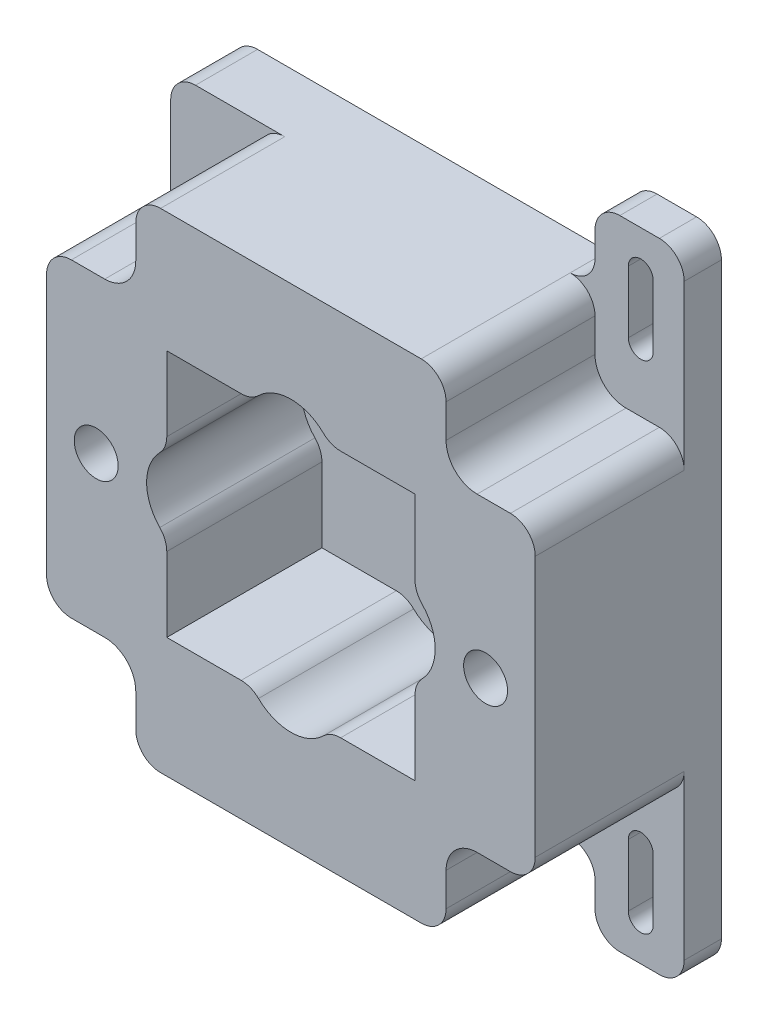
SolidWorks part; units mm, degrees
ref_plane "Front Plane" through (0, 0, 0) normal (0, 0, 1) x (1, 0, 0)
ref_plane "Top Plane" through (0, 0, 0) normal (0, 1, 0) x (1, 0, 0)
ref_plane "Right Plane" through (0, 0, 0) normal (1, 0, 0) x (0, 0, -1)
sketch "Sketch1" plane through (0, 0, 0) normal (0, 0, 1) x (1, 0, 0)
  line L1 (25, -25) -> (-25, -25)
  line L3 (25, -25) -> (25, 25)
  line L6 (25, 25) -> (-25, 25)
  line L7 (-25, -25) -> (-25, 25)
  line L8 (25, -25) -> (-25, 25) construction
  line L9 (25, 25) -> (-25, -25) construction
  point P0 (0, 0)
  dimension "D1" = 50
extrude "Boss-Extrude1" add sketch "Sketch1" along normal blind 6.35 contours L7 L1 L3 L6 region at (0, 0, 0)
sketch "Sketch6" plane through (0, 0, 6.35) normal (0, 0, 1) x (1, 0, 0)
  line L0 (15.875, 25) -> (-15.875, 25)
  line L1 (12.7, -12.7) -> (-12.7, -12.7)
  line L2 (12.7, -12.7) -> (12.7, 12.7)
  line L3 (12.7, 12.7) -> (-12.7, 12.7)
  line L4 (-12.7, -12.7) -> (-12.7, 12.7)
  line L5 (12.7, -12.7) -> (-12.7, 12.7) construction
  line L6 (12.7, 12.7) -> (-12.7, -12.7) construction
  line L7 (-25, -15.875) -> (-25, 15.875)
  line L8 (15.875, -25) -> (-15.875, -25)
  line L9 (25, -15.875) -> (25, 15.875)
  line L10 (-15.875, 19.05) -> (-15.875, 25)
  line L11 (-19.05, 15.875) -> (-25, 15.875)
  line L12 (25, 25) -> (-25, 25) construction
  line L13 (-25, -25) -> (-25, 25) construction
  line L14 (19.05, 15.875) -> (25, 15.875)
  line L15 (15.875, 19.05) -> (15.875, 25)
  line L16 (15.875, -19.05) -> (15.875, -25)
  line L17 (19.05, -15.875) -> (25, -15.875)
  line L18 (-19.05, -15.875) -> (-25, -15.875)
  line L19 (-15.875, -19.05) -> (-15.875, -25)
  line L20 (25, -25) -> (25, 25) construction
  line L21 (25, -25) -> (-25, -25) construction
  line L22 (0, 0) -> (0, -42.4127) construction
  line L23 (25, -25) -> (-25, -25) construction
  line L24 (-25, -25) -> (-25, 25) construction
  line L25 (0, 0) -> (48.4549, 0) construction
  arc A0 (-19.05, 15.875) -> (-15.875, 19.05) centre (-19.05, 19.05) ccw
  arc A1 (15.875, 19.05) -> (19.05, 15.875) centre (19.05, 19.05) ccw
  arc A2 (19.05, -15.875) -> (15.875, -19.05) centre (19.05, -19.05) ccw
  arc A3 (-15.875, -19.05) -> (-19.05, -15.875) centre (-19.05, -19.05) ccw
  point P0 (0, 0)
  point P33 (0, 0)
  dimension "D4" = 3.175
  dimension "D1" = 25.4
  dimension "D2" = 31.75
  dimension "D3" = 31.75
extrude "Boss-Extrude3" add sketch "Sketch6" along normal blind 12.7 contours L19 L8 L16 L17 L9 L14 L15 L0 L10 L11 L7 L18 L1 L4 L3 L2 region at (15.1679, 22.025, 6.35)
sketch "Sketch10" plane through (0, 0, 19.05) normal (0, 0, 1) x (1, 0, 0)
  line L12 (-12.7, -12.7) -> (12.7, -12.7)
  line L13 (12.7, -12.7) -> (12.7, 12.7)
  line L14 (12.7, 12.7) -> (-12.7, 12.7)
  line L15 (-12.7, 12.7) -> (-12.7, -12.7)
  dimension "D1" = 25.4
  dimension "D2" = 25.4
extrude "Cut-Extrude2" cut sketch "Sketch10" against normal blind 15.875
fillet "Fillet3" radius 2.54 8 edges at (-15.875, -25, 12.7) (15.875, -25, 12.7) (25, -15.875, 12.7) (25, 15.875, 12.7) (15.875, 25, 12.7) (-15.875, 25, 12.7) (-25, -15.875, 12.7) (-25, 15.875, 12.7)
sketch "Sketch11" plane through (0, 0, 6.35) normal (0, 0, 1) x (1, 0, 0)
  line L0 (33.4433, 630.1123) -> (32.9175, 610.2798) construction
  line L1 (25, -25) -> (15.875, -25)
  line L2 (25, -25) -> (25, -32.62)
  line L3 (25, -32.62) -> (15.875, -32.62)
  line L4 (15.875, -25) -> (15.875, -32.62)
  line L5 (15.875, -19.05) -> (15.875, -22.46) construction
  dimension "D1" = 7.62
extrude "Boss-Extrude4" add sketch "Sketch11" against normal up to surface (6.35 mm away) up to face at (0, 0, 0)
fillet "Fillet4" radius 2.54 2 edges at (15.875, -32.62, 3.175) (25, -32.62, 3.175)
sketch "Sketch12" plane through (0, 0, 6.35) normal (0, 0, 1) x (1, 0, 0)
  line L0 (25, -30.08) -> (25, -13.335) construction
  line L2 (19.05, -15.875) -> (22.46, -15.875) construction
  line L3 (20.555, -28.575) -> (20.555, -22.225) construction
  line L4 (19.285, -28.575) -> (19.285, -22.225)
  line L5 (21.825, -28.575) -> (21.825, -22.225)
  circle A0 centre (20.555, -25.4) radius 1.27
  arc A1 (19.285, -28.575) -> (21.825, -28.575) centre (20.555, -28.575) ccw
  arc A2 (21.825, -22.225) -> (19.285, -22.225) centre (20.555, -22.225) ccw
  point P9 (20.555, -25.4)
  dimension "D1" = 2.54
  dimension "D2" = 9.525
  dimension "D3" = 6.35
  dimension "D4" = 4.445
extrude "Cut-Extrude3" cut sketch "Sketch12" against normal through all contours L4 A1 L5 A0 | A0 | L5 A2 L4 A0 | L3 A0 region at (20.016, -25.4, 6.35) region at (21.4892, -26.3342, 6.35) region at (21.094, -25.4, 6.35) region at (19.6208, -24.4658, 6.35)
mirror "Mirror1" about plane through (0, 0, 0) normal (0, 1, 0) of "Cut-Extrude3", "Fillet4", "Boss-Extrude4"
fillet "Fillet5" radius 2.54 4 edges at (-25, 25, 3.175) (-25, -25, 3.175) (15.875, 25, 3.175) (15.875, -25, 3.175)
sketch "Sketch13" plane through (0, 0, 6.35) normal (0, 0, 1) x (1, 0, 0)
  line L0 (22.46, 32.62) -> (18.415, 32.62) construction
  line L1 (15.875, 30.08) -> (15.875, 27.54) construction
  line L2 (15.875, 22.46) -> (15.875, 19.05) construction
  line L3 (19.05, 15.875) -> (22.46, 15.875) construction
  line L4 (25, 13.335) -> (25, 30.08) construction
  line L5 (15.875, -27.54) -> (15.875, -30.08) construction
  line L6 (18.415, -32.62) -> (22.46, -32.62) construction
  line L7 (25, -30.08) -> (25, -13.335) construction
  line L8 (22.46, -15.875) -> (19.05, -15.875) construction
  line L9 (15.875, -19.05) -> (15.875, -22.46) construction
  line L10 (22.46, 32.62) -> (18.415, 32.62)
  line L11 (15.875, 30.08) -> (15.875, 27.54)
  line L12 (15.875, 22.46) -> (15.875, 19.05)
  line L13 (19.05, 15.875) -> (22.46, 15.875)
  line L14 (25, 13.335) -> (25, 30.08)
  line L15 (15.875, -27.54) -> (15.875, -30.08)
  line L16 (18.415, -32.62) -> (22.46, -32.62)
  line L17 (25, -30.08) -> (25, -13.335)
  line L18 (22.46, -15.875) -> (19.05, -15.875)
  line L19 (15.875, -19.05) -> (15.875, -22.46)
  arc A0 (18.415, 32.62) -> (15.875, 30.08) centre (18.415, 30.08) ccw construction
  arc A1 (13.335, 25) -> (15.875, 27.54) centre (13.335, 27.54) ccw construction
  arc A2 (15.875, 22.46) -> (13.335, 25) centre (13.335, 22.46) ccw construction
  arc A3 (15.875, 19.05) -> (19.05, 15.875) centre (19.05, 19.05) ccw construction
  arc A4 (25, 13.335) -> (22.46, 15.875) centre (22.46, 13.335) ccw construction
  arc A5 (25, 30.08) -> (22.46, 32.62) centre (22.46, 30.08) ccw construction
  arc A6 (13.335, -25) -> (15.875, -22.46) centre (13.335, -22.46) ccw construction
  arc A7 (15.875, -27.54) -> (13.335, -25) centre (13.335, -27.54) ccw construction
  arc A8 (15.875, -30.08) -> (18.415, -32.62) centre (18.415, -30.08) ccw construction
  arc A9 (22.46, -32.62) -> (25, -30.08) centre (22.46, -30.08) ccw construction
  arc A10 (22.46, -15.875) -> (25, -13.335) centre (22.46, -13.335) ccw construction
  arc A11 (19.05, -15.875) -> (15.875, -19.05) centre (19.05, -19.05) ccw construction
  arc A12 (18.415, 32.62) -> (15.875, 30.08) centre (18.415, 30.08) ccw
  arc A13 (13.335, 25) -> (15.875, 27.54) centre (13.335, 27.54) ccw
  arc A14 (15.875, 22.46) -> (13.335, 25) centre (13.335, 22.46) ccw
  arc A15 (15.875, 19.05) -> (19.05, 15.875) centre (19.05, 19.05) ccw
  arc A16 (25, 13.335) -> (22.46, 15.875) centre (22.46, 13.335) ccw
  arc A17 (25, 30.08) -> (22.46, 32.62) centre (22.46, 30.08) ccw
  arc A18 (13.335, -25) -> (15.875, -22.46) centre (13.335, -22.46) ccw
  arc A19 (15.875, -27.54) -> (13.335, -25) centre (13.335, -27.54) ccw
  arc A20 (15.875, -30.08) -> (18.415, -32.62) centre (18.415, -30.08) ccw
  arc A21 (22.46, -32.62) -> (25, -30.08) centre (22.46, -30.08) ccw
  arc A22 (22.46, -15.875) -> (25, -13.335) centre (22.46, -13.335) ccw
  arc A23 (19.05, -15.875) -> (15.875, -19.05) centre (19.05, -19.05) ccw
extrude "Cut-Extrude4" cut sketch "Sketch13" against normal blind 2.54
sketch "Sketch14" plane through (0, 0, 3.175) normal (0, 0, 1) x (1, 0, 0)
  circle A0 centre (-10, 0) radius 4.7625
  circle A1 centre (0, -10) radius 4.7625
  circle A2 centre (10, 0) radius 4.7625
  circle A3 centre (0, 10) radius 4.7625
  dimension "D1" = 9.525
extrude "Cut-Extrude5" cut sketch "Sketch14" along normal through all
fillet "Fillet6" radius 2.54 8 edges at (3.9232, 12.7, 11.1125) (-3.9232, 12.7, 11.1125) (12.7, 3.9232, 11.1125) (12.7, -3.9232, 11.1125) (3.9232, -12.7, 11.1125) (-3.9232, -12.7, 11.1125) (-12.7, -3.9232, 11.1125) (-12.7, 3.9232, 11.1125)
hole_wizard "#10 Clearance Hole1" positions "Sketch15" profile "Sketch16" hole size "#10" standard "ANSI Inch" end condition through all
sketch "Sketch15" plane through (0, 0, 3.175) normal (0, 0, 1) x (1, 0, 0)
  point P0 (-10, 0)
  point P3 (0, 10)
  point P5 (10, 0)
  point P8 (0, -10)
sketch "Sketch16" plane through (-10, 0, 3.175) normal (1, 0, 0) x (0, -1, 0)
  line L0 (0, 0) -> (0, 3.175)
  line L1 (0, 3.175) -> (2.5527, 3.175)
  line L2 (2.5527, 3.175) -> (2.5527, 0)
  line L5 (2.5527, 0) -> (0, 0)
  line L11 (0, -6.35) -> (0, 107.95) construction
  dimension "Thru Hole Dia." = 5.1054
  dimension "Thru Hole Depth" = 3.175
hole_wizard "#8 Clearance Hole1" positions "Sketch17" profile "Sketch18" hole size "#8" standard "ANSI Inch" end condition through all
sketch "Sketch17" plane through (0, 0, 19.05) normal (0, 0, 1) x (1, 0, 0)
  line L0 (-25, 0) -> (25, 0) construction
  line L1 (-25, 13.335) -> (-25, -13.335) construction
  line L2 (25, -13.335) -> (25, 13.335) construction
  point P0 (-19.92, 0)
  point P2 (19.92, 0)
  dimension "D1" = 5.08
  dimension "D2" = 5.08
sketch "Sketch18" plane through (-19.92, 0, 19.05) normal (1, 0, 0) x (0, -1, 0)
  line L0 (0, 0) -> (0, 19.05)
  line L1 (0, 19.05) -> (2.2479, 19.05)
  line L2 (2.2479, 19.05) -> (2.2479, 0)
  line L5 (2.2479, 0) -> (0, 0)
  line L11 (0, -6.35) -> (0, 107.95) construction
  dimension "Thru Hole Dia." = 4.4958
  dimension "Thru Hole Depth" = 19.05
